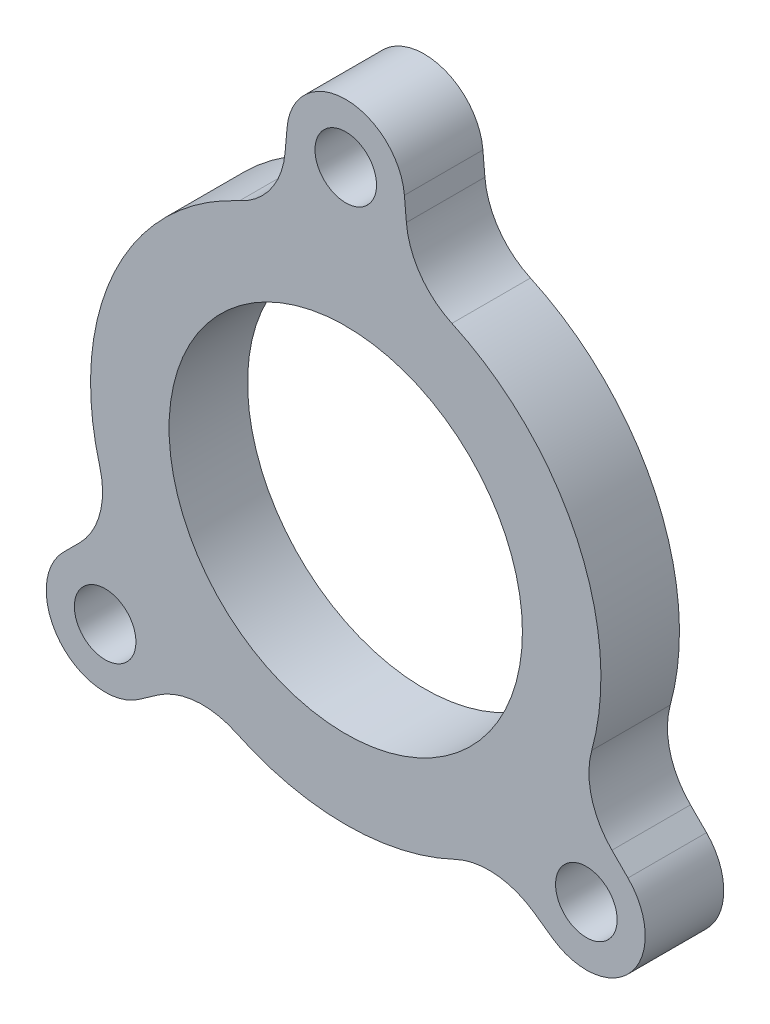
SolidWorks part; units mm, degrees
material "6061-T6 (SS)"
ref_plane "Front Plane" through (0, 0, 0) normal (0, 0, 1) x (1, 0, 0)
ref_plane "Top Plane" through (0, 0, 0) normal (0, 1, 0) x (1, 0, 0)
ref_plane "Right Plane" through (0, 0, 0) normal (1, 0, 0) x (0, 0, -1)
sketch "Sketch1" plane through (0, 0, 0) normal (0, 0, 1) x (1, 0, 0)
  line L0 (0, 0) -> (0, 25.4) construction
  line L1 (0, 0) -> (19.4575, -16.3268) construction
  line L2 (0, 0) -> (-19.4575, -16.3268) construction
  line L3 (-4.7444, 25.8151) -> (-5.2569, 19.9567)
  line L4 (4.7444, 25.8151) -> (5.2569, 19.9567)
  line L5 (22.8251, -12.9592) -> (18.6668, -8.8009)
  line L6 (16.7259, -20.228) -> (11.9087, -16.855)
  line L7 (-16.7259, -20.228) -> (-11.9087, -16.855)
  line L8 (-18.6668, -8.8009) -> (-22.8251, -12.9592)
  circle A0 centre (19.4575, -16.3268) radius 4.7625
  circle A1 centre (0, 25.4) radius 4.7625
  circle A2 centre (-19.4575, -16.3268) radius 4.7625
  circle A3 centre (19.4575, -16.3268) radius 2.4892
  circle A4 centre (-19.4575, -16.3268) radius 2.4892
  circle A5 centre (0, 25.4) radius 2.4892
  circle A6 centre (0, 0) radius 14.2875
  circle A7 centre (0, 0) radius 20.6375
  dimension "D1" = 9.525
  dimension "D4" = 4.9784
  dimension "D13" = 6.35
  dimension "D14" = 28.575
  dimension "D2" = 25.4
  dimension "D5" = 130
  dimension "D6" = 130
  dimension "D7" = 5
  dimension "D8" = 5
  dimension "D9" = 5
  dimension "D10" = 5
  dimension "D11" = 5
  dimension "D12" = 5
extrude "Boss-Extrude1" add sketch "Sketch1" along normal mid plane 6.35 contours A7 A6 | A7 L4 A1 L3 | A7 L6 A0 L5 | A7 L8 A2 L7 | A2 A4 | A1 A5 | A0 A3 | A7 A2 L7 | A7 L6 A0 | A7 A1 L3 region at (-3.9194, 21.5843, 0) region at (0, 30.0278, 0) region at (-2.5754, 19.8877, 0) region at (3.9194, 21.5843, 0) region at (-19.0539, -10.8717, 0) region at (-19.2557, -11.7034, 0) region at (-14.0152, -16.8766, 0) region at (19.0539, -10.8717, 0) region at (14.0152, -16.8766, 0) region at (23.7331, -14.5558, 0)
fillet "Fillet1" radius 6.35 6 edges at (18.6668, -8.8009, 0) (11.9087, -16.855, 0) (-11.9087, -16.855, 0) (-18.6668, -8.8009, 0) (-5.2569, 19.9567, 0) (5.2569, 19.9567, 0)
